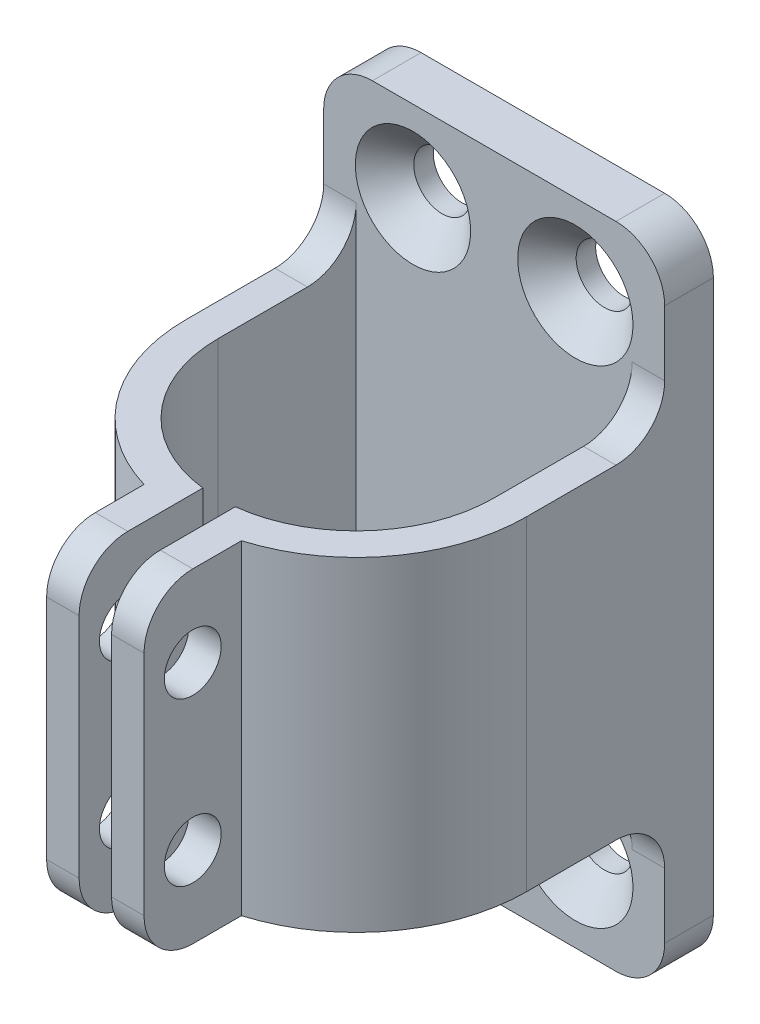
SolidWorks part; units mm, degrees
ref_plane "Front Plane" through (0, 0, 0) normal (0, 0, 1) x (1, 0, 0)
ref_plane "Top Plane" through (0, 0, 0) normal (0, 1, 0) x (1, 0, 0)
ref_plane "Right Plane" through (0, 0, 0) normal (1, 0, 0) x (0, 0, -1)
sketch "Sketch1" plane through (0, 0, 0) normal (0, 0, 1) x (1, 0, 0)
  line L1 (-10.5, 20) -> (10.5, 20)
  line L2 (-10.5, 20) -> (-10.5, -20)
  line L3 (-10.5, -20) -> (10.5, -20)
  line L4 (10.5, 20) -> (10.5, -20)
  line L5 (-10.5, 20) -> (10.5, -20) construction
  line L6 (-10.5, -20) -> (10.5, 20) construction
  line L7 (-5, 15) -> (5, 15) construction
  line L8 (-5, 15) -> (-5, -15) construction
  line L9 (-5, -15) -> (5, -15) construction
  line L10 (5, 15) -> (5, -15) construction
  line L11 (-5, 15) -> (5, -15) construction
  line L12 (-5, -15) -> (5, 15) construction
  circle A0 centre (-5, 15) radius 1.75
  circle A1 centre (5, 15) radius 1.75
  circle A2 centre (5, -15) radius 1.75
  circle A3 centre (-5, -15) radius 1.75
  point P0 (0, 0)
  point P5 (0, 0)
  point P15 (-15.0152, 34.4498)
  dimension "D1" = 3.5
  dimension "D2" = 10
  dimension "D3" = 30
  dimension "D4" = 5
  dimension "D5" = 21
extrude "Boss-Extrude1" add sketch "Sketch1" along normal blind 3
sketch "Sketch3" plane through (0, 0, 0) normal (0, 1, 0) x (1, 0, 0)
  line L0 (10.5, -3) -> (-10.5, -3) construction
  line L10 (-8.5, -3) -> (-8.5, -11.5)
  line L25 (-27.6265, -787.8792) -> (29.8019, -2.8849) construction
  line L26 (-24.1749, -713.2878) -> (27.6541, -4.8322) construction
  line L27 (10.5004, -4.4068) -> (27.6541, -4.8322) construction
  line L28 (-10.5, -10.4105) -> (-24.1749, -713.2878) construction
  line L29 (-11.6968, 30.8925) -> (-27.6265, -787.8792) construction
  line L30 (10.5463, -2.4073) -> (29.8019, -2.8849) construction
  line L33 (-10.5, -10.4105) -> (-10.5, -10.4105) construction
  line L37 (-3, -21.5623) -> (-3, -27.5623)
  line L38 (-3, -27.5623) -> (-1, -27.5623)
  line L41 (-1, -27.5623) -> (-1, -19.941)
  line L44 (-11.6968, 30.8925) -> (-8.5, -3) construction
  line L46 (-10.5, -3) -> (-8.5, -3)
  line L48 (8.4285, -2.3627) -> (10.5463, -2.4073) construction
  line L49 (0, 0) -> (0, -27.5623) construction
  line L50 (8.4285, -2.3627) -> (0.8972, -3.0475) construction
  line L51 (8.4982, -4.3646) -> (7.7643, -4.4313) construction
  line L52 (8.4982, -4.3646) -> (10.5004, -4.4068) construction
  line L53 (10.5, 0) -> (-10.5, 0) construction
  line L54 (-10.5, -10.4105) -> (-10.5, -11.5) construction
  line L55 (-10.5, -11.5) -> (-10.5, -3)
  line L56 (10.5, -11.5) -> (10.5, -3)
  line L57 (10.5, -3) -> (8.5, -3)
  line L58 (1, -27.5623) -> (1, -19.941)
  line L59 (3, -27.5623) -> (1, -27.5623)
  line L60 (3, -21.5623) -> (3, -27.5623)
  line L61 (8.5, -3) -> (8.5, -11.5)
  arc A0 (-8.5, -11.5) -> (-1, -19.941) centre (0, -11.5) ccw
  arc A1 (-10.5, -11.5) -> (-3, -21.5623) centre (0, -11.5) ccw
  arc A3 (-10.5, -11.5) -> (7.7643, -4.4313) centre (0, -11.5) ccw construction
  arc A6 (-8.5, -11.5) -> (0.8972, -3.0475) centre (0, -11.5) ccw construction
  arc A7 (10.5, -11.5) -> (3, -21.5623) centre (0, -11.5) cw
  arc A8 (8.5, -11.5) -> (1, -19.941) centre (0, -11.5) cw
  dimension "D1" = 17
  dimension "D2" = 2
  dimension "D3" = 2
  dimension "D4" = 6
  dimension "D5" = 1
extrude "Boss-Extrude2" add sketch "Sketch3" against normal mid plane 20
sketch "Sketch4" plane through (3, 0, 0) normal (1, 0, 0) x (0, 0, -1)
  line L0 (-24.5623, 10) -> (-24.5623, -10) construction
  line L9 (-27.5623, 0) -> (-27.5623, 10) construction
  line L10 (-27.5623, 0) -> (-27.5623, -10) construction
  line L12 (-21.5623, -10) -> (-27.5623, -10) construction
  line L13 (-27.5623, 10) -> (-21.5623, 10) construction
  line L14 (-27.5623, -10) -> (-27.5623, 10) construction
  circle A0 centre (-24.5623, 5) radius 1.75
  circle A1 centre (-24.5623, -5) radius 1.75
  point P2 (-23.0623, 20)
  point P4 (-23.0623, -20)
  point P11 (-25.5623, 0)
  point P12 (0, 0)
  point P15 (-25.3353, 0)
  point P16 (-25.5623, 10)
  point P17 (0, 0)
  point P18 (-25.5623, -10)
  point P20 (0, 0)
  point P23 (-27.5623, 5)
  point P25 (-25.5623, -15)
  point P26 (-25.5623, -4.9496)
  point P28 (-27.5623, -5)
  point P29 (0, 0)
  point P30 (0, 0)
  point P31 (0, 0)
  point P32 (0, 0)
  point P33 (-25.5623, -20)
  point P35 (0, 0)
  point P37 (0, 0)
  point P38 (-25.4487, 19.8671)
  point P39 (-25.5623, 20)
  point P41 (0, 0)
  dimension "D1" = 3.5
  dimension "D2" = 3.5
extrude "Cut-Extrude1" cut sketch "Sketch4" against normal through all both and the other way through all
chamfer "Chamfer1" distance 1.8 angle 45 4 edges at (6.75, -15, 3) (-3.25, -15, 3) (6.75, 15, 3) (-3.25, 15, 3)
fillet "Fillet1" radius 3 8 edges at (-10.5, 20, 1.5) (-10.5, -20, 1.5) (10.5, -20, 1.5) (10.5, 20, 1.5) (2, -10, 27.5623) (-2, -10, 27.5623) (-2, 10, 27.5623) (2, 10, 27.5623)
fillet "Fillet2" radius 3 4 edges at (9.5, -10, 3) (-9.5, -10, 3) (9.5, 10, 3) (-9.5, 10, 3)
